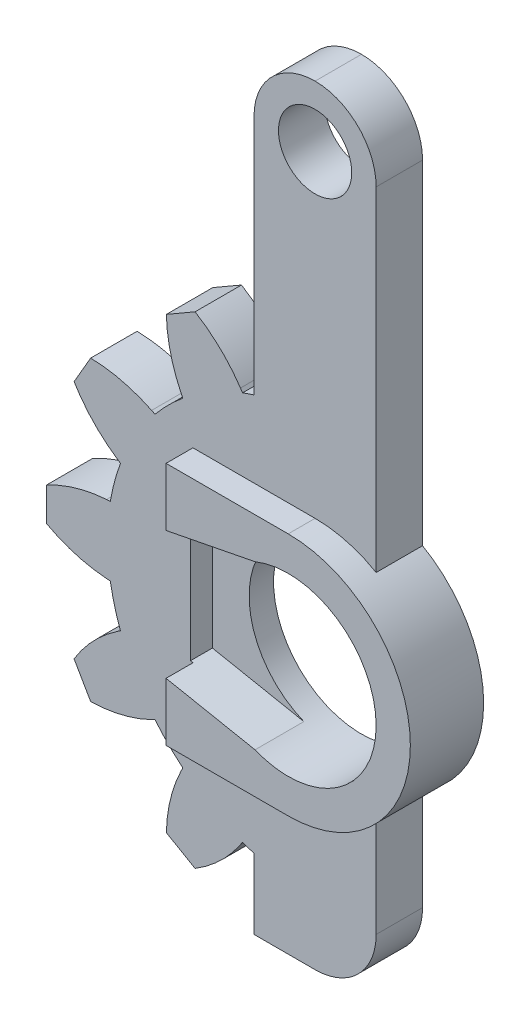
SolidWorks part; units mm, degrees
ref_plane "Front Plane" through (0, 0, 0) normal (0, 0, 1) x (1, 0, 0)
ref_plane "Top Plane" through (0, 0, 0) normal (0, 1, 0) x (1, 0, 0)
ref_plane "Right Plane" through (0, 0, 0) normal (1, 0, 0) x (0, 0, -1)
sketch "Sketch1" plane through (0, 0, 0) normal (0, 0, 1) x (1, 0, 0)
  circle A0 centre (0, 0) radius 8.5
  dimension "D1" = 17
extrude "Boss-Extrude1" add sketch "Sketch1" along normal blind 1.9
sketch "Sketch2" plane through (0, 0, 1.9) normal (0, 0, 1) x (1, 0, 0)
  line L0 (0, 0) -> (0, 10.5876) construction
  line L1 (0, 0) -> (1.4399, 10.9374) construction
  line L2 (0, 0) -> (-1.4446, 10.9725) construction
  circle A0 centre (0, 0) radius 10 construction
  dimension "D3" = 20
  dimension "D1" = 7.5
  dimension "D2" = 7.5
ref_point "Point3"
ref_point "Point4"
sketch "Sketch3" plane through (0, 0, 1.9) normal (0, 0, 1) x (1, 0, 0)
  line L0 (-1.3053, 9.9144) -> (-1.5091, 7)
  line L1 (-1.5091, 7) -> (1.5091, 7)
  line L2 (1.3053, 9.9144) -> (1.5091, 7)
  line L3 (1.3053, 9.9144) -> (0.6785, 11)
  line L4 (-1.3053, 9.9144) -> (-0.6785, 11)
  line L5 (-0.6785, 11) -> (0.6785, 11)
  dimension "D1" = 11
  dimension "D2" = 7
  dimension "D3" = 60
  dimension "D4" = 86
  dimension "D5" = 60
  dimension "D6" = 86
extrude "Boss-Extrude2" add sketch "Sketch3" against normal blind 1.9
pattern_circular "CirPattern2" count 12 over 360 about axis through (0, 0, 1.9) along (0, 0, -1) of "Boss-Extrude2"
fillet "Fillet5" radius 6 12 edges at (9.2388, 3.8268, 0.95) (6.0876, 7.9335, 0.95) (1.3053, 9.9144, 0.95) (-3.8268, 9.2388, 0.95) (-7.9335, 6.0876, 0.95) (-9.9144, 1.3053, 0.95) (-9.2388, -3.8268, 0.95) (-6.0876, -7.9335, 0.95) (-1.3053, -9.9144, 0.95) (3.8268, -9.2388, 0.95) (7.9335, -6.0876, 0.95) (9.9144, -1.3053, 0.95)
fillet "Fillet6" radius 6 12 edges at (7.9335, 6.0876, 0.95) (3.8268, 9.2388, 0.95) (-1.3053, 9.9144, 0.95) (-6.0876, 7.9335, 0.95) (-9.2388, 3.8268, 0.95) (-9.9144, -1.3053, 0.95) (-7.9335, -6.0876, 0.95) (-3.8268, -9.2388, 0.95) (1.3053, -9.9144, 0.95) (6.0876, -7.9335, 0.95) (9.2388, -3.8268, 0.95) (9.9144, 1.3053, 0.95)
sketch "Sketch4" plane through (0, 0, 0) normal (0, 0, -1) x (-1, 0, 0)
  line L0 (-2.5, 20.5) -> (-2.5, 4.3301)
  line L1 (-2.5, -4.3301) -> (-2.5, -11)
  line L2 (2.5, 4.3301) -> (2.5, 20.5)
  line L3 (2.5, 20.5) -> (-2.5, 20.5)
  line L4 (-2.5, -11) -> (2.5, -11)
  line L5 (2.5, -11) -> (2.5, -4.3301)
  arc A0 (-2.5, 4.3301) -> (-2.5, -4.3301) centre (0, 0) ccw
  arc A1 (2.5, -4.3301) -> (2.5, 4.3301) centre (0, 0) ccw
  dimension "D1" = 10
  dimension "D2" = 2.5
  dimension "D3" = 20.5
  dimension "D4" = 11
extrude "Boss-Extrude3" add sketch "Sketch4" against normal blind 1.9
sketch "Sketch6" plane through (0, 0, 0) normal (0, 0, -1) x (-1, 0, 0)
  line L0 (-2.5, 13.1922) -> (-2.5, -11)
  line L1 (-2.5, 20.5) -> (-2.5, 8.124) construction
  line L2 (-2.5, -11) -> (-13.5179, -11)
  line L3 (-13.5179, -11) -> (-13.5179, 13.1922)
  line L4 (-13.5179, 13.1922) -> (-2.5, 13.1922)
extrude "Cut-Extrude2" cut sketch "Sketch6" against normal through all
sketch "Sketch8" plane through (0, 0, 0) normal (0, 0, -1) x (-1, 0, 0)
  circle A0 centre (0, 0) radius 5
  dimension "D1" = 10
extrude "Boss-Extrude4" add sketch "Sketch8" against normal blind 3
sketch "Sketch14" plane through (0, 0, 0) normal (0, 0, -1) x (-1, 0, 0)
  line L0 (0, 5) -> (5, 5)
  line L1 (5, 5) -> (5, -5)
  line L2 (5, -5) -> (0, -5)
  line L3 (0, -5) -> (0, 5)
  arc A0 (-2.5, 4.3301) -> (-2.5, -4.3301) centre (0, 0) ccw construction
  dimension "D1" = 5
  dimension "D2" = 5
  dimension "D3" = 5
extrude "Boss-Extrude8" add sketch "Sketch14" against normal blind 3
sketch "Sketch17" plane through (0, 0, 1.9) normal (0, 0, 1) x (1, 0, 0)
  circle A0 centre (0, 18) radius 1.5
  dimension "D1" = 3
  dimension "D2" = 18
extrude "Cut-Extrude10" cut sketch "Sketch17" against normal through all
sketch "Sketch18" plane through (0, 0, 0) normal (0, 0, 1) x (1, 0, 0)
  line L0 (0, 0) -> (-11, 0) construction
  line L1 (-11, 0.6785) -> (-11, -0.6785) construction
fillet "Fillet9" radius 2.5 2 edges at (-2.5, 20.5, 0.95) (2.5, 20.5, 0.95)
fillet "Fillet10" radius 2.5 1 edges at (2.5, -11, 0.95)
sketch "Sketch19" plane through (0, 0, 3) normal (0, 0, 1) x (1, 0, 0)
  line L0 (0, 3.6) -> (-5.1029, 2.6)
  line L1 (-5.1029, 2.6) -> (-5.1029, -2.6)
  line L2 (-5.1029, -2.6) -> (0, -3.6)
  line L3 (0, -3.6) -> (0, 3.6)
  point P2 (0, 0)
  point P5 (-5.1029, 0)
  dimension "D1" = 7.2
  dimension "D2" = 5.2
  dimension "D3" = 5.2
extrude "Cut-Extrude11" cut sketch "Sketch19" against normal blind 2
sketch "Sketch20" plane through (0, 0, 3) normal (0, 0, 1) x (1, 0, 0)
  circle A0 centre (0, 0) radius 3.6
  dimension "D1" = 7.2
extrude "Cut-Extrude12" cut sketch "Sketch20" against normal through all
